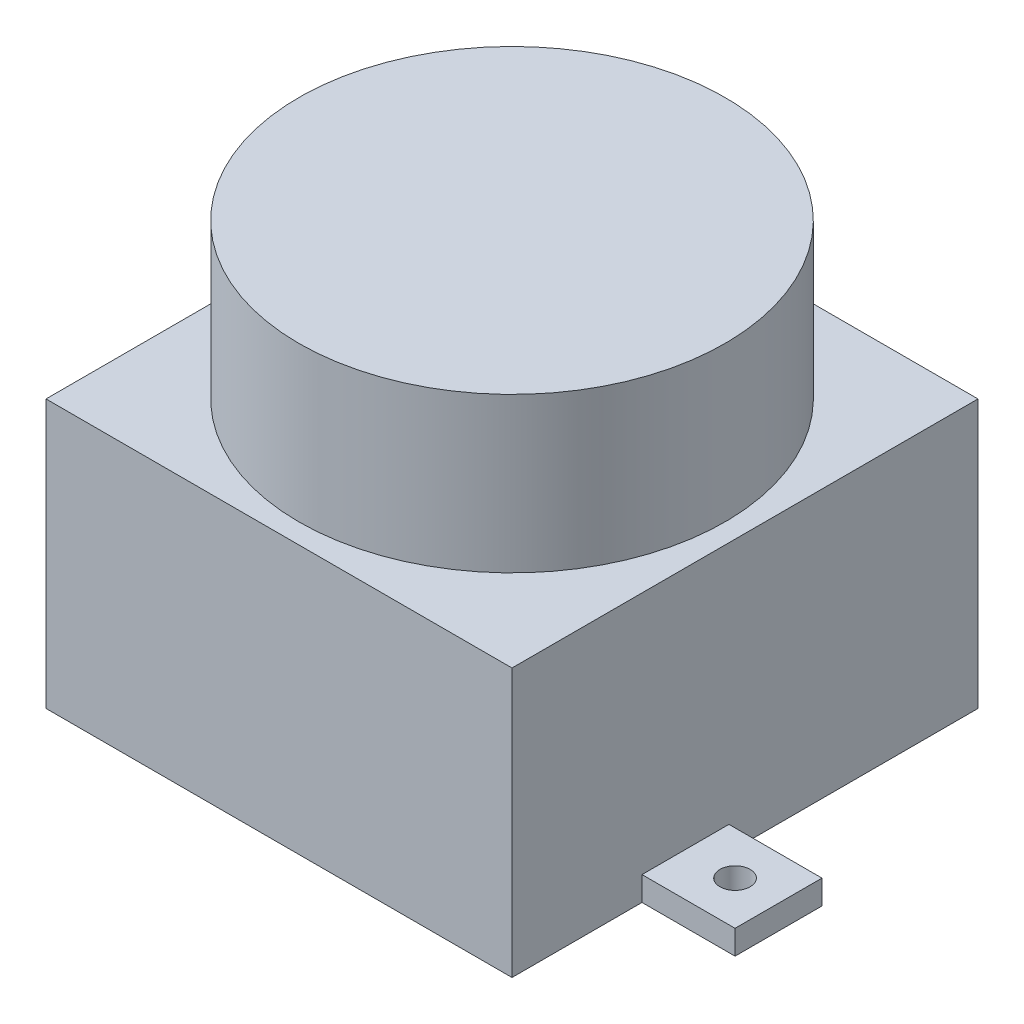
SolidWorks part; units mm, degrees
ref_plane "Front Plane" through (0, 0, 0) normal (0, 0, 1) x (1, 0, 0)
ref_plane "Top Plane" through (0, 0, 0) normal (0, 1, 0) x (1, 0, 0)
ref_plane "Right Plane" through (0, 0, 0) normal (1, 0, 0) x (0, 0, -1)
sketch "SK_Housing" plane through (0, 0, 0) normal (0, 1, 0) x (1, 0, 0)
  line L1 (-19.295, 19.295) -> (19.295, 19.295)
  line L2 (-19.295, 19.295) -> (-19.295, -19.295)
  line L3 (-19.295, -19.295) -> (19.295, -19.295)
  line L4 (19.295, 19.295) -> (19.295, -19.295)
  dimension "D1" = 38.59
  dimension "D2" = 38.59
  dimension "D3" = 19.295
  dimension "D4" = 19.295
extrude "EX_Housing" add sketch "SK_Housing" along normal blind 22.2
sketch "SK_Ears" plane through (0, 0, 0) normal (0, 1, 0) x (1, 0, 0)
  line L1 (19, -1.33) -> (27, -1.33)
  line L2 (19, -1.33) -> (19, -8.53)
  line L3 (19, -8.53) -> (27, -8.53)
  line L4 (27, -1.33) -> (27, -8.53)
  line L6 (-27, -1.33) -> (-19, -1.33)
  line L7 (-27, -1.33) -> (-27, -8.53)
  line L8 (-27, -8.53) -> (-19, -8.53)
  line L9 (-19, -1.33) -> (-19, -8.53)
  line L11 (-3.6, 27) -> (3.6, 27)
  line L12 (-3.6, 27) -> (-3.6, 19)
  line L13 (-3.6, 19) -> (3.6, 19)
  line L14 (3.6, 27) -> (3.6, 19)
  dimension "D1" = 7.2
  dimension "D2" = 8
  dimension "D3" = 1.33
  dimension "D4" = 19
  dimension "D5" = 7.2
  dimension "D6" = 8
  dimension "D7" = 1.33
  dimension "D8" = 27
  dimension "D9" = 8
  dimension "D10" = 7.2
  dimension "D11" = 27
  dimension "D12" = 3.6
extrude "EX_Ears" add sketch "SK_Ears" along normal blind 2
sketch "SK_Holes_3x" plane through (0, 0, 0) normal (0, 1, 0) x (1, 0, 0)
  circle A0 centre (23.4, -4.93) radius 1.25
  circle A1 centre (-23.4, -4.93) radius 1.25
  circle A2 centre (0, 23.39) radius 1.25
  dimension "D3" = 2.5
  dimension "D6" = 2.5
  dimension "D8" = 2.5
  dimension "D1" = 4.93
  dimension "D2" = 23.4
  dimension "D4" = 4.93
  dimension "D5" = 23.4
  dimension "D7" = 23.39
extrude "CUT_Holes_3x" cut sketch "SK_Holes_3x" along normal blind 2
ref_plane "PL_Zp22_2" through (0, 22.2, 0) normal (0, 1, 0) x (1, 0, 0)
sketch "SK_Dome" plane through (0, 22.2, 0) normal (0, 1, 0) x (1, 0, 0)
  circle A0 centre (0, 0) radius 17.645
  dimension "D1" = 35.29
extrude "EX_Dome" add sketch "SK_Dome" along normal blind 12.8
ref_axis "AX_X" through (0, 0, -29.3148) along (0, 0, 1)
ref_axis "AX_Y" through (29.7, 0, 0) along (-1, 0, 0)
ref_axis "AX_Z" through (0, 36.75, 0) along (0, -1, 0)
ref_plane "PL_Zp27_2" through (0, 27.2, 0) normal (0, 1, 0) x (1, 0, 0)
sketch "SK_F_laser" plane through (0, 27.2, 0) normal (0, 1, 0) x (1, 0, 0)
  point P0 (0, 0)
